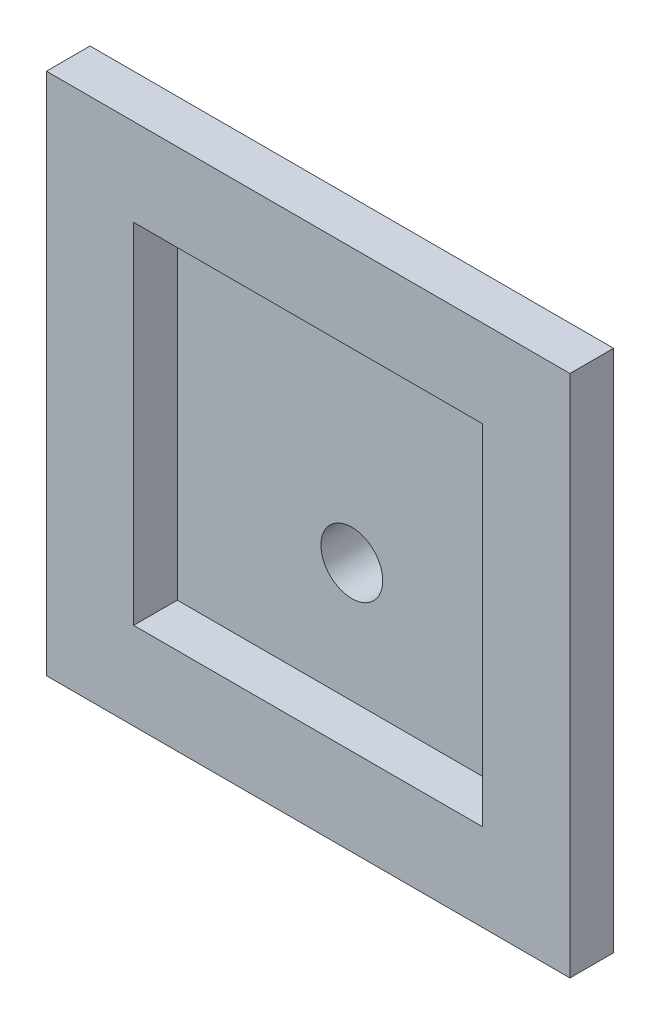
SolidWorks part; units mm, degrees
ref_plane "Front Plane" through (0, 0, 0) normal (0, 0, 1) x (1, 0, 0)
ref_plane "Top Plane" through (0, 0, 0) normal (0, 1, 0) x (1, 0, 0)
ref_plane "Right Plane" through (0, 0, 0) normal (1, 0, 0) x (0, 0, -1)
sketch "Sketch1" plane through (0, 0, 0) normal (0, 0, 1) x (1, 0, 0)
  line L1 (19.05, -19.05) -> (-19.05, -19.05)
  line L2 (19.05, -19.05) -> (19.05, 19.05)
  line L3 (19.05, 19.05) -> (-19.05, 19.05)
  line L4 (-19.05, -19.05) -> (-19.05, 19.05)
  line L5 (19.05, -19.05) -> (-19.05, 19.05) construction
  line L6 (19.05, 19.05) -> (-19.05, -19.05) construction
  line L7 (15.875, -15.875) -> (-15.875, -15.875)
  line L8 (15.875, -15.875) -> (15.875, 15.875)
  line L9 (15.875, 15.875) -> (-15.875, 15.875)
  line L10 (-15.875, -15.875) -> (-15.875, 15.875)
  line L11 (15.875, -15.875) -> (-15.875, 15.875) construction
  line L12 (15.875, 15.875) -> (-15.875, -15.875) construction
  point P0 (0, 0)
  point P6 (0, 0)
  dimension "D1" = 38.1
  dimension "D2" = 31.75
extrude "Boss-Extrude1" add sketch "Sketch1" against normal blind 3.175
extrude "Boss-Extrude2" add sketch "Sketch1<2>" against normal blind 6.35 contours L10 L7 L8 L9 region at (0, 0, 0)
sketch "Sketch1<2>" plane through (0, 0, 0) normal (0, 0, 1) x (1, 0, 0) same geometry as "Sketch1"
shell "Shell1" thickness 3.175 removed face at (0, 0, 0)
hole_wizard "M4 Clearance Hole1" positions "Sketch5" profile "Sketch3" hole size "M4" standard "ANSI Metric" end condition through all
sketch "Sketch5" plane through (0, 0, -3.175) normal (0, 0, 1) x (1, 0, 0)
  point P0 (0, -4)
  point P4 (0, 0)
  dimension "D1" = 4
sketch "Sketch3" plane through (0, -4, -3.175) normal (1, 0, 0) x (0, -1, 0)
  line L0 (0, 0) -> (0, 3.175)
  line L1 (0, 3.175) -> (2.25, 3.175)
  line L2 (2.25, 3.175) -> (2.25, 0)
  line L5 (2.25, 0) -> (0, 0)
  line L11 (0, -6.35) -> (0, 107.95) construction
  dimension "Thru Hole Dia." = 4.5
  dimension "Thru Hole Depth" = 3.175
